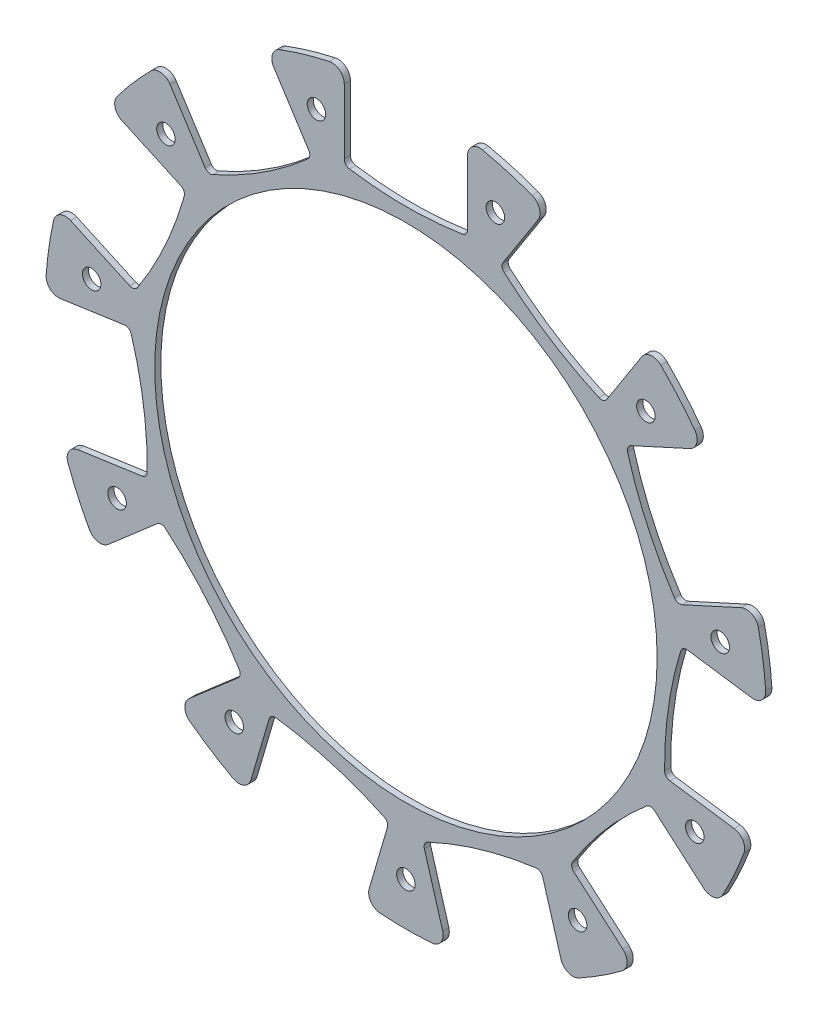
SolidWorks part; units mm, degrees
material "合金钢"
ref_plane "前视基准面" through (0, 0, 0) normal (0, 0, 1) x (1, 0, 0)
ref_plane "上视基准面" through (0, 0, 0) normal (0, 1, 0) x (1, 0, 0)
ref_plane "右视基准面" through (0, 0, 0) normal (1, 0, 0) x (0, 0, -1)
sketch "草图2" plane through (0, 0, 0) normal (0, 0, 1) x (1, 0, 0)
  line L0 (12.85, 52.4) -> (12.85, 55.6) construction
  line L1 (12.85, 55.6) -> (10, 55.6) construction
  line L2 (10, 52.4) -> (12.85, 52.4) construction
  line L3 (9.35, 50.9) -> (10, 50.9) construction
  line L4 (10, 50.9) -> (10, 57.1) construction
  line L5 (10, 57.1) -> (9.35, 57.1) construction
  line L6 (9.35, 46.1078) -> (9.35, 61.8922) construction
  line L7 (8.4948, 45.1184) -> (8.4948, 62.8816) construction
  line L8 (-8.4948, 62.8816) -> (-8.4948, 45.1184) construction
  line L9 (-9.35, 61.8922) -> (-9.35, 46.1078) construction
  line L10 (-10, 50.9) -> (-9.35, 50.9) construction
  line L11 (-9.35, 57.1) -> (-10, 57.1) construction
  line L12 (-10, 57.1) -> (-10, 50.9) construction
  line L13 (-10, 55.6) -> (-12.85, 55.6) construction
  line L14 (-12.85, 52.4) -> (-10, 52.4) construction
  line L15 (-12.85, 55.6) -> (-12.85, 52.4) construction
  line L16 (-8.4948, 54) -> (8.4948, 54) construction
  line L17 (10, 57.639) -> (10, 43.8392)
  line L18 (-10, 57.639) -> (-10, 43.8392)
  line L19 (39.5745, 43.0826) -> (32.1138, 31.4735)
  line L20 (22.7494, 53.8954) -> (15.2887, 42.2863)
  line L21 (56.5844, 14.8478) -> (44.0317, 9.1151)
  line L22 (48.2761, 33.0404) -> (35.7234, 27.3078)
  line L23 (55.6291, -18.1011) -> (41.9698, -16.1372)
  line L24 (58.4754, 1.6953) -> (44.8161, 3.6592)
  line L25 (37.012, -45.303) -> (26.5829, -36.2661)
  line L26 (50.1092, -30.188) -> (39.6801, -21.1511)
  line L27 (6.6438, -58.1215) -> (2.756, -44.8807)
  line L28 (25.8337, -52.4869) -> (21.9459, -39.2461)
  line L29 (-25.8337, -52.4869) -> (-21.9459, -39.2461)
  line L30 (-6.6438, -58.1215) -> (-2.756, -44.8807)
  line L31 (-50.1092, -30.188) -> (-39.6801, -21.1511)
  line L32 (-37.012, -45.303) -> (-26.5829, -36.2661)
  line L33 (-58.4754, 1.6953) -> (-44.8161, 3.6592)
  line L34 (-55.6291, -18.1011) -> (-41.9698, -16.1372)
  line L35 (-48.2761, 33.0404) -> (-35.7234, 27.3078)
  line L36 (-56.5844, 14.8478) -> (-44.0317, 9.1151)
  line L37 (-22.7494, 53.8954) -> (-15.2887, 42.2863)
  line L38 (-39.5745, 43.0826) -> (-32.1138, 31.4735)
  line L39 (0, 44.5) -> (0, 43) construction
  arc A0 (9.35, 61.8922) -> (8.4948, 62.8816) centre (8.35, 61.8922) ccw construction
  arc A1 (8.4948, 45.1184) -> (9.35, 46.1078) centre (8.35, 46.1078) ccw construction
  arc A2 (-8.4948, 45.1184) -> (8.4948, 45.1184) centre (0, 103.1567) ccw construction
  arc A3 (8.4948, 62.8816) -> (-8.4948, 62.8816) centre (0, 4.8433) ccw construction
  arc A4 (-8.4948, 62.8816) -> (-9.35, 61.8922) centre (-8.35, 61.8922) ccw construction
  arc A5 (-9.35, 46.1078) -> (-8.4948, 45.1184) centre (-8.35, 46.1078) ccw construction
  circle A6 centre (0, 0) radius 58.5 construction
  arc A7 (-10, 43.8392) -> (10, 43.8392) centre (0, 103) ccw
  arc A8 (15.2887, 42.2863) -> (32.1138, 31.4735) centre (55.686, 86.6491) ccw
  arc A9 (35.7234, 27.3078) -> (44.0317, 9.1151) centre (93.6921, 42.7877) ccw
  arc A10 (44.8161, 3.6592) -> (41.9698, -16.1372) centre (101.9516, -14.6584) ccw
  arc A11 (39.6801, -21.1511) -> (26.5829, -36.2661) centre (77.8422, -67.4507) ccw
  arc A12 (21.9459, -39.2461) -> (2.756, -44.8807) centre (29.0185, -98.8278) ccw
  arc A13 (-2.756, -44.8807) -> (-21.9459, -39.2461) centre (-29.0185, -98.8278) ccw
  arc A14 (-26.5829, -36.2661) -> (-39.6801, -21.1511) centre (-77.8422, -67.4507) ccw
  arc A15 (-41.9698, -16.1372) -> (-44.8161, 3.6592) centre (-101.9516, -14.6584) ccw
  arc A16 (-44.0317, 9.1151) -> (-35.7234, 27.3078) centre (-93.6921, 42.7877) ccw
  arc A17 (-32.1138, 31.4735) -> (-15.2887, 42.2863) centre (-55.686, 86.6491) ccw
  arc A18 (-22.7494, 53.8954) -> (-10, 57.639) centre (0, 0) cw
  arc A19 (10, 57.639) -> (22.7494, 53.8954) centre (0, 0) cw
  arc A20 (39.5745, 43.0826) -> (48.2761, 33.0404) centre (0, 0) cw
  arc A21 (56.5844, 14.8478) -> (58.4754, 1.6953) centre (0, 0) cw
  arc A22 (55.6291, -18.1011) -> (50.1092, -30.188) centre (0, 0) cw
  arc A23 (37.012, -45.303) -> (25.8337, -52.4869) centre (0, 0) cw
  arc A24 (6.6438, -58.1215) -> (-6.6438, -58.1215) centre (0, 0) cw
  arc A25 (-48.2761, 33.0404) -> (-39.5745, 43.0826) centre (0, 0) cw
  arc A26 (-56.5844, 14.8478) -> (-58.4754, 1.6953) centre (0, 0) ccw
  arc A27 (-55.6291, -18.1011) -> (-50.1092, -30.188) centre (0, 0) ccw
  arc A28 (-37.012, -45.303) -> (-25.8337, -52.4869) centre (0, 0) ccw
  circle A29 centre (0, 0) radius 63.5 construction
  circle A30 centre (0, 0) radius 40.75
  circle A31 centre (0, -51.5) radius 1.5
  circle A32 centre (-27.843, -43.3246) radius 1.5
  circle A33 centre (-46.846, -21.3939) radius 1.5
  circle A34 centre (-50.9758, 7.3292) radius 1.5
  circle A35 centre (-38.9211, 33.7253) radius 1.5
  circle A36 centre (-14.5092, 49.4139) radius 1.5
  circle A37 centre (14.5092, 49.4139) radius 1.5
  circle A38 centre (38.9211, 33.7253) radius 1.5
  circle A39 centre (50.9758, 7.3292) radius 1.5
  circle A40 centre (46.846, -21.3939) radius 1.5
  circle A41 centre (27.843, -43.3246) radius 1.5
  point P37 (-12.85, 54)
  point P41 (-9.675, 57.1)
  point P42 (-9.675, 50.9)
  point P43 (0, 63.5)
  point P44 (0, 44.5)
  point P45 (-10, 54)
  point P46 (-9.35, 54)
  point P47 (9.35, 54)
  point P48 (10, 54)
  point P49 (12.85, 54)
  point P54 (0, 54)
  point P108 (0, 0)
  point P132 (0, 0)
  dimension "D1" = 25.7
  dimension "D8" = 1
  dimension "D9" = 58.6567
  dimension "D11" = 117
  dimension "D12" = 60
  dimension "D15" = 127
  dimension "D16" = 81.5
  dimension "D17" = 3
  dimension "D2" = 3.2
  dimension "D3" = 6.2
  dimension "D4" = 20
  dimension "D5" = 19
  dimension "D6" = 18.7
  dimension "D7" = 54
  dimension "D10" = 16.9896
  dimension "D13" = 1.5
  dimension "D18" = 51.5
  dimension "D14" = 11
  dimension "D19" = 11
extrude "凸台-拉伸1" add sketch "草图2" along normal blind 1
fillet "圆角1" radius 1 22 edges at (10, 43.8392, 0.5) (-10, 43.8392, 0.5) (-15.2887, 42.2863, 0.5) (-32.1138, 31.4735, 0.5) (-35.7234, 27.3078, 0.5) (-44.0317, 9.1151, 0.5) (-44.8161, 3.6592, 0.5) (-41.9698, -16.1372, 0.5) (-39.6801, -21.1511, 0.5) (-26.5829, -36.2661, 0.5) (-21.9459, -39.2461, 0.5) (-2.756, -44.8807, 0.5) (2.756, -44.8807, 0.5) (21.9459, -39.2461, 0.5) (26.5829, -36.2661, 0.5) (39.6801, -21.1511, 0.5) (41.9698, -16.1372, 0.5) (44.8161, 3.6592, 0.5) (44.0317, 9.1151, 0.5) (35.7234, 27.3078, 0.5) (32.1138, 31.4735, 0.5) (15.2887, 42.2863, 0.5)
fillet "圆角2" radius 2 22 edges at (10, 57.639, 0.5) (-10, 57.639, 0.5) (-22.7494, 53.8954, 0.5) (-39.5745, 43.0826, 0.5) (-48.2761, 33.0404, 0.5) (-56.5844, 14.8478, 0.5) (-58.4754, 1.6953, 0.5) (-55.6291, -18.1011, 0.5) (-50.1092, -30.188, 0.5) (-37.012, -45.303, 0.5) (-25.8337, -52.4869, 0.5) (-6.6438, -58.1215, 0.5) (6.6438, -58.1215, 0.5) (25.8337, -52.4869, 0.5) (37.012, -45.303, 0.5) (50.1092, -30.188, 0.5) (55.6291, -18.1011, 0.5) (58.4754, 1.6953, 0.5) (56.5844, 14.8478, 0.5) (48.2761, 33.0404, 0.5) (39.5745, 43.0826, 0.5) (22.7494, 53.8954, 0.5)
ref_axis "基准轴1" through (0, 0, 1) along (0, 0, -1)
